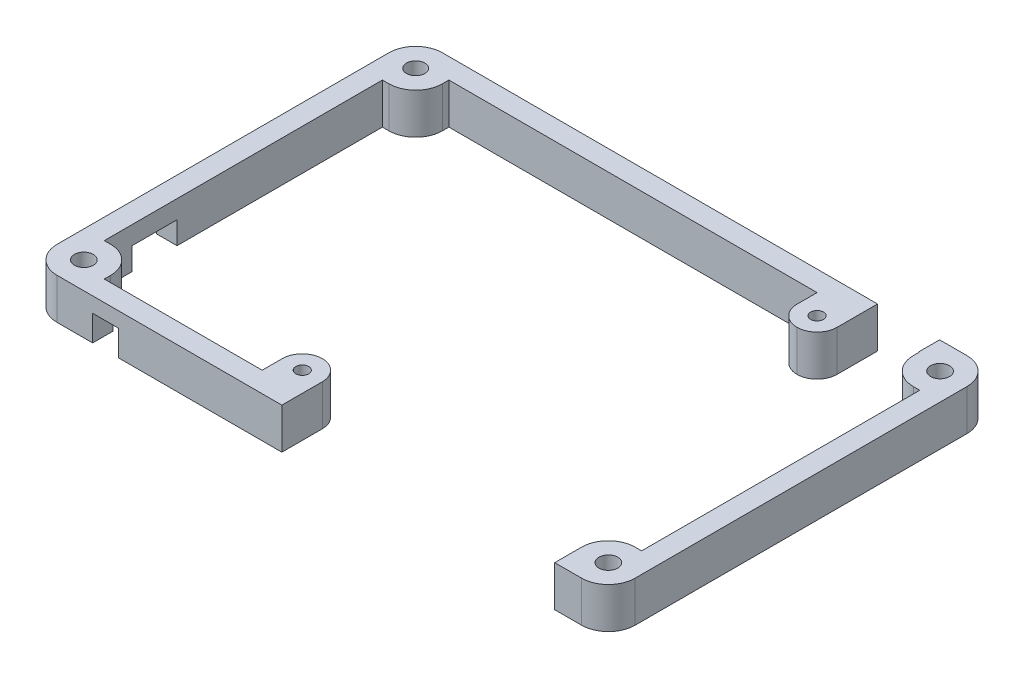
SolidWorks part; units mm, degrees
material "Rubber"
ref_plane "Front" through (0, 0, 0) normal (0, 0, 1) x (1, 0, 0)
ref_plane "Top" through (0, 0, 0) normal (0, 1, 0) x (1, 0, 0)
ref_plane "Right" through (0, 0, 0) normal (1, 0, 0) x (0, 0, -1)
sketch "Sketch1" plane through (0, 0, 0) normal (0, 1, 0) x (1, 0, 0)
  line L0 (-45, 0) -> (45, 0) construction
  line L1 (-45, 30) -> (45, 30) construction
  line L2 (-45, 30) -> (-45, -30) construction
  line L3 (-45, -30) -> (45, -30) construction
  line L4 (45, 30) -> (45, -30) construction
  line L5 (0, -30) -> (0, 30) construction
  line L6 (41.825, 26.825) -> (41.825, -26.825) construction
  line L7 (-41.825, -26.825) -> (41.825, -26.825) construction
  line L8 (-41.825, 26.825) -> (-41.825, -26.825) construction
  line L9 (-41.825, 26.825) -> (41.825, 26.825) construction
  line L10 (40.825, 25.825) -> (40.825, -25.825) construction
  line L11 (-40.825, -25.825) -> (40.825, -25.825) construction
  line L12 (-40.825, 25.825) -> (-40.825, -25.825) construction
  line L13 (-40.825, 25.825) -> (40.825, 25.825) construction
  line L14 (40.825, 21.65) -> (45, 21.65) construction
  line L15 (40.825, -21.65) -> (45, -21.65) construction
  line L16 (36.65, -25.825) -> (36.65, -30) construction
  line L17 (-36.65, -25.825) -> (-36.65, -30) construction
  line L18 (-40.825, -21.65) -> (-45, -21.65) construction
  line L19 (-36.65, 25.825) -> (-36.65, 30) construction
  line L20 (-40.825, 21.65) -> (-45, 21.65) construction
  line L21 (36.65, 25.825) -> (36.65, 30) construction
  line L22 (40.825, -25.825) -> (41.825, -25.825) construction
  circle A0 centre (-40.825, -25.825) radius 1 construction
  circle A1 centre (40.825, -25.825) radius 1 construction
  circle A2 centre (40.825, 25.825) radius 1 construction
  circle A3 centre (-40.825, 25.825) radius 1 construction
  circle A4 centre (40.825, -25.825) radius 4.175 construction
  circle A5 centre (40.825, 25.825) radius 4.175 construction
  circle A6 centre (-40.825, 25.825) radius 4.175 construction
  circle A7 centre (-40.825, -25.825) radius 4.175 construction
  dimension "D1" = 90
  dimension "D2" = 60
  dimension "D4" = 1
  dimension "D3" = 3.175
sketch "Sketch2" plane through (0, 0, 0) normal (0, 1, 0) x (1, 0, 0)
  line L0 (-45, 30) -> (-45, -30) construction
  line L1 (-45, -30) -> (45, -30) construction
  line L2 (45, 30) -> (45, -30) construction
  line L3 (-45, 30) -> (45, 30) construction
  line L4 (40.825, 21.65) -> (45, 21.65) construction
  line L5 (36.65, 25.825) -> (36.65, 30) construction
  line L6 (-36.65, 25.825) -> (-36.65, 30) construction
  line L7 (-40.825, 21.65) -> (-45, 21.65) construction
  line L8 (-36.65, -25.825) -> (-36.65, -30) construction
  line L9 (-40.825, -21.65) -> (-45, -21.65) construction
  line L10 (36.65, -25.825) -> (36.65, -30) construction
  line L11 (40.825, -21.65) -> (45, -21.65) construction
  line L16 (-45, 25.825) -> (-45, -25.825)
  line L17 (-40.825, -30) -> (40.825, -30)
  line L18 (45, 25.825) -> (45, -25.825)
  line L19 (-40.825, 30) -> (40.825, 30)
  line L20 (40.825, 21.65) -> (41.825, 21.65)
  line L21 (36.65, 25.825) -> (36.65, 26.825)
  line L22 (-36.65, 25.825) -> (-36.65, 26.825)
  line L23 (-40.825, 21.65) -> (-41.825, 21.65)
  line L24 (-36.65, -25.825) -> (-36.65, -26.825)
  line L25 (-40.825, -21.65) -> (-41.825, -21.65)
  line L26 (36.65, -25.825) -> (36.65, -26.825)
  line L27 (40.825, -21.65) -> (41.825, -21.65)
  line L28 (41.825, 26.825) -> (41.825, -26.825) construction
  line L29 (-36.65, -26.825) -> (36.65, -26.825)
  line L30 (-41.825, 26.825) -> (41.825, 26.825) construction
  line L31 (-41.825, 26.825) -> (-41.825, -26.825) construction
  line L32 (-36.65, 26.825) -> (36.65, 26.825)
  line L33 (-41.825, 21.65) -> (-41.825, -21.65)
  line L34 (41.825, 21.65) -> (41.825, -21.65)
  line L35 (-41.825, -26.825) -> (41.825, -26.825) construction
  circle A0 centre (40.825, 25.825) radius 4.175 construction
  circle A1 centre (40.825, 25.825) radius 1 construction
  circle A2 centre (-40.825, 25.825) radius 4.175 construction
  circle A3 centre (-40.825, 25.825) radius 1 construction
  circle A4 centre (-40.825, -25.825) radius 4.175 construction
  circle A5 centre (40.825, -25.825) radius 4.175 construction
  arc A6 (45, 25.825) -> (40.825, 30) centre (40.825, 25.825) ccw
  circle A7 centre (40.825, 25.825) radius 1 construction
  arc A8 (-40.825, 30) -> (-45, 25.825) centre (-40.825, 25.825) ccw
  circle A9 centre (-40.825, 25.825) radius 1 construction
  arc A10 (-36.65, -25.825) -> (-40.825, -21.65) centre (-40.825, -25.825) ccw
  arc A11 (40.825, -21.65) -> (36.65, -25.825) centre (40.825, -25.825) ccw
  circle A12 centre (-40.825, -25.825) radius 1 construction
  circle A13 centre (40.825, -25.825) radius 1 construction
  circle A14 centre (-40.825, -25.825) radius 1 construction
  circle A15 centre (40.825, -25.825) radius 1 construction
  arc A16 (-40.825, 21.65) -> (-36.65, 25.825) centre (-40.825, 25.825) ccw
  arc A17 (-45, -25.825) -> (-40.825, -30) centre (-40.825, -25.825) ccw
  arc A18 (40.825, -30) -> (45, -25.825) centre (40.825, -25.825) ccw
  arc A19 (36.65, 25.825) -> (40.825, 21.65) centre (40.825, 25.825) ccw
extrude "Boss-Extrude3" add sketch "Sketch2" along normal blind 6.35
sketch "Sketch3" plane through (0, 0, -30) normal (0, 0, -1) x (-1, 0, 0)
  line L0 (-40.825, 6.35) -> (40.825, 6.35) construction
  line L1 (-36.566, 6.35) -> (-26.9027, 6.35)
  line L2 (-36.566, 6.35) -> (-36.566, 0)
  line L3 (-36.566, 0) -> (-26.9027, 0)
  line L4 (-26.9027, 6.35) -> (-26.9027, 0)
  line L5 (-40.825, 0) -> (40.825, 0) construction
extrude "Cut-Extrude1" cut sketch "Sketch3" against normal up to vertex (3.175 mm away) up to point (36.65, 6.35, -26.825)
sketch "Sketch4" plane through (0, 0, 30) normal (0, 0, 1) x (1, 0, 0)
  line L0 (-40.825, 6.35) -> (40.825, 6.35) construction
  line L1 (36.65, 6.35) -> (-5.825, 6.35)
  line L2 (36.65, 6.35) -> (36.65, 0)
  line L3 (36.65, 0) -> (-5.825, 0)
  line L4 (-5.825, 6.35) -> (-5.825, 0)
  line L5 (-40.825, 0) -> (40.825, 0) construction
  line L6 (-40.825, 6.35) -> (-40.825, 0) construction
  dimension "D1" = 35
extrude "Cut-Extrude2" cut sketch "Sketch4" against normal up to vertex (8.35 mm away)
sketch "Sketch5" plane through (-45, 0, 0) normal (-1, 0, 0) x (0, 0, 1)
  line L0 (13.825, 0) -> (25.825, 0) construction
  line L1 (25.825, 6.35) -> (25.825, 0) construction
  line L3 (17.325, 3.5) -> (10.325, 3.5)
  line L4 (17.325, 3.5) -> (17.325, -3.5)
  line L5 (17.325, -3.5) -> (10.325, -3.5)
  line L6 (10.325, 3.5) -> (10.325, -3.5)
  line L7 (17.325, 3.5) -> (10.325, -3.5) construction
  line L8 (17.325, -3.5) -> (10.325, 3.5) construction
  dimension "D1" = 12
  dimension "D2" = 7
  dimension "D3" = 7
extrude "Cut-Extrude3" cut sketch "Sketch5" against normal up to surface (3.175 mm away) up to face at (-41.825, 3.175, 0)
sketch "Sketch6" plane through (0, 0, 0) normal (0, -1, 0) x (1, 0, 0)
  circle A0 centre (40.825, 25.825) radius 1.4732
  circle A1 centre (40.825, -25.8149) radius 1.4732
  dimension "D1" = 2.9464
  dimension "D2" = 2.9464
extrude "Cut-Extrude4" cut sketch "Sketch6" against normal up to surface (6.35 mm away) up to face at (39.763, 6.35, -3.8321)
sketch "Sketch7" plane through (0, 0, 0) normal (0, -1, 0) x (1, 0, 0)
  circle A0 centre (-40.825, -25.825) radius 1.4224
  circle A1 centre (-40.825, 25.825) radius 1.4732
  circle A2 centre (-40.825, 25.825) radius 1 construction
  dimension "D1" = 2.8448
  dimension "D2" = 2.9464
extrude "Cut-Extrude5" cut sketch "Sketch7" against normal up to surface (6.35 mm away) up to face at (-27.5872, 6.35, 0)
sketch "Sketch8" plane through (0, 0, 26.825) normal (0, 0, -1) x (-1, 0, 0)
  line L0 (36.65, 0) -> (5.825, 0) construction
  line L1 (5.825, 6.35) -> (12.065, 6.35)
  line L2 (5.825, 6.35) -> (5.825, 0)
  line L3 (5.825, 0) -> (12.065, 0)
  line L4 (12.065, 6.35) -> (12.065, 0)
  dimension "D1" = 6.24
extrude "Boss-Extrude4" add sketch "Sketch8" along normal blind 6.24
sketch "Sketch9" plane through (0, 0, -26.825) normal (0, 0, 1) x (1, 0, 0)
  line L0 (26.9027, 0) -> (-36.65, 0) construction
  line L1 (26.9027, 6.35) -> (20.6627, 6.35)
  line L2 (26.9027, 6.35) -> (26.9027, 0)
  line L3 (26.9027, 0) -> (20.6627, 0)
  line L4 (20.6627, 6.35) -> (20.6627, 0)
  dimension "D1" = 6.24
extrude "Boss-Extrude5" add sketch "Sketch9" along normal blind 6.24
sketch "Sketch10" plane through (0, 0, 0) normal (0, -1, 0) x (-1, 0, 0)
  line L0 (-20.6627, 26.825) -> (-26.9027, 20.585) construction
  line L1 (12.065, -26.825) -> (5.825, -20.585) construction
  circle A0 centre (-23.7827, 23.705) radius 1
  circle A1 centre (8.945, -23.705) radius 1
extrude "Cut-Extrude6" cut sketch "Sketch10" against normal through all
fillet "Fillet1" radius 3.12 4 edges at (-12.065, 3.175, 20.585) (-5.825, 3.175, 20.585) (26.9027, 3.175, -20.585) (20.6627, 3.175, -20.585)
sketch "Sketch11" plane through (0, 0, 30) normal (0, 0, 1) x (1, 0, 0)
  line L0 (-40.825, 0) -> (-5.825, 0) construction
  line L1 (-35.285, 4) -> (-31.285, 4)
  line L2 (-35.285, 4) -> (-35.285, 0)
  line L3 (-35.285, 0) -> (-31.285, 0)
  line L4 (-31.285, 4) -> (-31.285, 0)
  line L5 (-35.285, 4) -> (-31.285, 0) construction
  line L6 (-35.285, 0) -> (-31.285, 4) construction
  line L7 (-40.825, 6.35) -> (-40.825, 0) construction
  point P0 (-33.285, 2)
  dimension "D1" = 4
  dimension "D2" = 4
  dimension "D3" = 5.54
extrude "Cut-Extrude7" cut sketch "Sketch11" against normal blind 10
